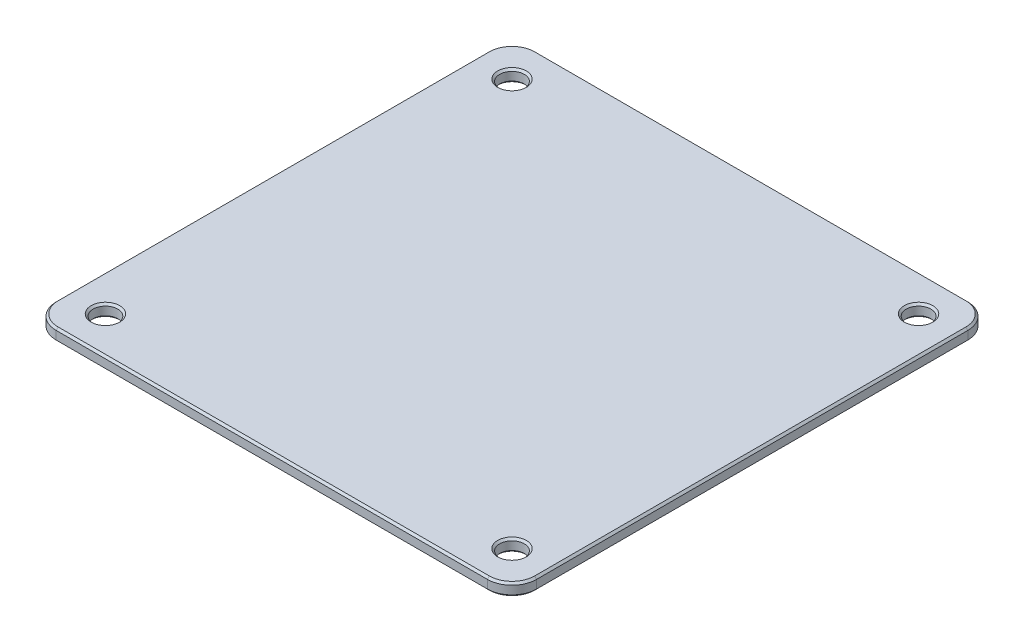
SolidWorks part; units mm, degrees
ref_plane "Front" through (0, 0, 0) normal (0, 0, 1) x (1, 0, 0)
ref_plane "Top" through (0, 0, 0) normal (0, 1, 0) x (1, 0, 0)
ref_plane "Right" through (0, 0, 0) normal (1, 0, 0) x (0, 0, -1)
sketch "Sketch2" plane through (0, 0, 0) normal (0, 1, 0) x (1, 0, 0)
  line L0 (26.1937, -26.1937) -> (26.1937, 26.1938) construction
  line L1 (-30.9563, -30.9562) -> (30.9562, -30.9562)
  line L2 (-30.9563, -30.9562) -> (-30.9563, 30.9563)
  line L3 (-30.9563, 30.9563) -> (30.9562, 30.9563)
  line L4 (30.9562, -30.9562) -> (30.9562, 30.9563)
  line L5 (-30.9563, -30.9562) -> (30.9562, 30.9563) construction
  line L6 (-30.9563, 30.9563) -> (30.9562, -30.9562) construction
  line L7 (26.1937, 26.1938) -> (-26.1937, 26.1937) construction
  line L8 (-26.1937, 26.1937) -> (-26.1937, -26.1937) construction
  line L9 (-26.1937, -26.1937) -> (26.1937, -26.1937) construction
  line L10 (26.1937, 26.1938) -> (30.9562, 26.1938) construction
  line L11 (26.1937, 26.1938) -> (26.1937, 30.9563) construction
  circle A0 centre (-26.1937, 26.1937) radius 1.5875
  circle A1 centre (26.1937, 26.1938) radius 1.5875
  circle A2 centre (26.1937, -26.1937) radius 1.5875
  circle A3 centre (-26.1937, -26.1937) radius 1.5875
  point P0 (0, 0)
  dimension "D3" = 3.175
  dimension "D1" = 61.9125
  dimension "D2" = 4.7625
extrude "Boss-Extrude1" add sketch "Sketch2" along normal blind 1.5875
fillet "Fillet1" radius 3.175 4 edges at (30.9562, 0.7937, 30.9562) (-30.9563, 0.7937, -30.9563) (30.9562, 0.7937, -30.9563) (-30.9563, 0.7937, 30.9562)
chamfer "Chamfer1" distance 0.254 angle 45 24 edges at (-26.1937, 0, 27.7812) (26.1937, 0, -24.6063) (30.0263, 0, -30.0263) (0, 0, -30.9563) (-30.0263, 0, -30.0263) (-30.9563, 0, 0) (-30.0263, 0, 30.0263) (0, 0, 30.9562) (30.0263, 0, 30.0263) (30.9562, 0, 0) (-26.1937, 0, -24.6062) (26.1937, 0, 27.7812) (-26.1937, 1.5875, 27.7812) (26.1937, 1.5875, 27.7812) (26.1937, 1.5875, -24.6063) (-26.1937, 1.5875, -24.6062) (-30.0263, 1.5875, 30.0263) (-30.9563, 1.5875, 0) (-30.0263, 1.5875, -30.0263) (0, 1.5875, -30.9563) (30.0263, 1.5875, -30.0263) (30.9562, 1.5875, 0) (30.0263, 1.5875, 30.0263) (0, 1.5875, 30.9562)
